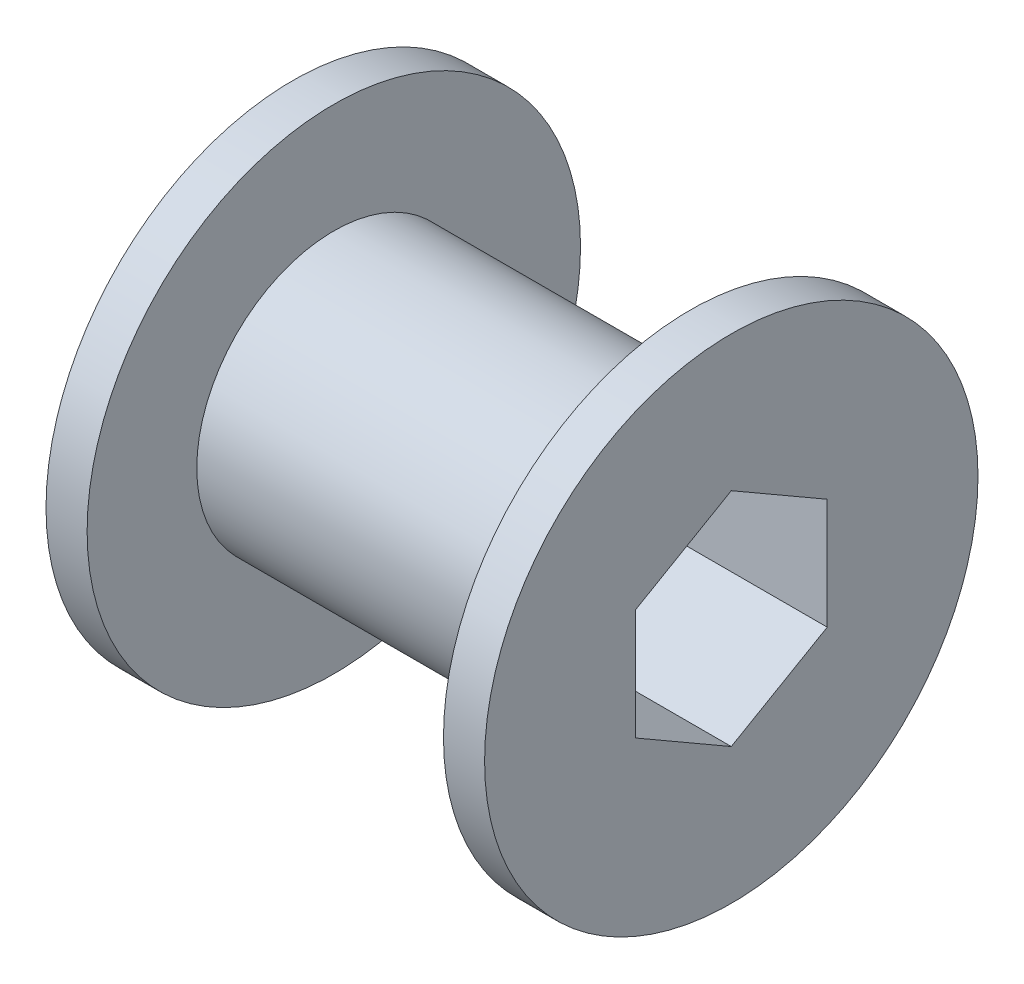
SolidWorks part; units mm, degrees
ref_plane "Front Plane" through (0, 0, 0) normal (0, 0, 1) x (1, 0, 0)
ref_plane "Top Plane" through (0, 0, 0) normal (0, 1, 0) x (1, 0, 0)
ref_plane "Right Plane" through (0, 0, 0) normal (1, 0, 0) x (0, 0, -1)
sketch "Sketch1" plane through (0, 0, 0) normal (1, 0, 0) x (0, 0, -1)
  circle A0 centre (0, 0) radius 2.5
  dimension "D1" = 5
extrude "Boss-Extrude1" add sketch "Sketch1" along normal mid plane 8
sketch "Sketch2" plane through (4, 0, 0) normal (1, 0, 0) x (0, 0, -1)
  circle A0 centre (0, 0) radius 4.5
  dimension "D1" = 9
extrude "Boss-Extrude2" add sketch "Sketch2" against normal blind 0.75
mirror "Mirror1" about plane through (0, 0, 0) normal (1, 0, 0) of "Boss-Extrude2"
sketch "Sketch3" plane through (0, 0, 0) normal (1, 0, 0) x (0, 0, -1)
  line L0 (1.75, 0) -> (1.75, 1.0104)
  line L1 (1.6, 0) -> (1.6, 0.9238) construction
  line L2 (1.6, -0.9238) -> (1.6, 0) construction
  line L3 (0.8, -1.3856) -> (1.6, -0.9238) construction
  line L4 (0, -1.8475) -> (0.8, -1.3856) construction
  line L5 (-0.8, -1.3856) -> (0, -1.8475) construction
  line L6 (-1.6, -0.9238) -> (-0.8, -1.3856) construction
  line L7 (-1.6, 0) -> (-1.6, -0.9238) construction
  line L8 (-1.6, 0.9238) -> (-1.6, 0) construction
  line L9 (-0.8, 1.3856) -> (-1.6, 0.9238) construction
  line L10 (0, 1.8475) -> (-0.8, 1.3856) construction
  line L11 (0.8, 1.3856) -> (0, 1.8475) construction
  line L12 (1.6, 0.9238) -> (0.8, 1.3856) construction
  line L13 (1.6, 0) -> (1.6, 0.9238) construction
  line L14 (1.6, -0.9238) -> (1.6, 0) construction
  line L15 (0.8, -1.3856) -> (1.6, -0.9238) construction
  line L16 (0, -1.8475) -> (0.8, -1.3856) construction
  line L17 (-0.8, -1.3856) -> (0, -1.8475) construction
  line L18 (-1.6, -0.9238) -> (-0.8, -1.3856) construction
  line L19 (-1.6, 0) -> (-1.6, -0.9238) construction
  line L20 (-1.6, 0.9238) -> (-1.6, 0) construction
  line L21 (-0.8, 1.3856) -> (-1.6, 0.9238) construction
  line L22 (0, 1.8475) -> (-0.8, 1.3856) construction
  line L23 (0.8, 1.3856) -> (0, 1.8475) construction
  line L24 (1.6, 0.9238) -> (0.8, 1.3856) construction
  line L25 (1.75, 1.0104) -> (0.875, 1.5155)
  line L26 (0.875, 1.5155) -> (0, 2.0207)
  line L27 (0, 2.0207) -> (-0.875, 1.5155)
  line L28 (-0.875, 1.5155) -> (-1.75, 1.0104)
  line L29 (-1.75, 1.0104) -> (-1.75, 0)
  line L30 (-1.75, 0) -> (-1.75, -1.0104)
  line L31 (-1.75, -1.0104) -> (-0.875, -1.5155)
  line L32 (-0.875, -1.5155) -> (0, -2.0207)
  line L33 (0, -2.0207) -> (0.875, -1.5155)
  line L34 (0.875, -1.5155) -> (1.75, -1.0104)
  line L35 (1.75, -1.0104) -> (1.75, 0)
  dimension "D1" = 0.15
extrude "M1.6 Nut" cut sketch "Sketch3" against normal through all both and the other way through all
